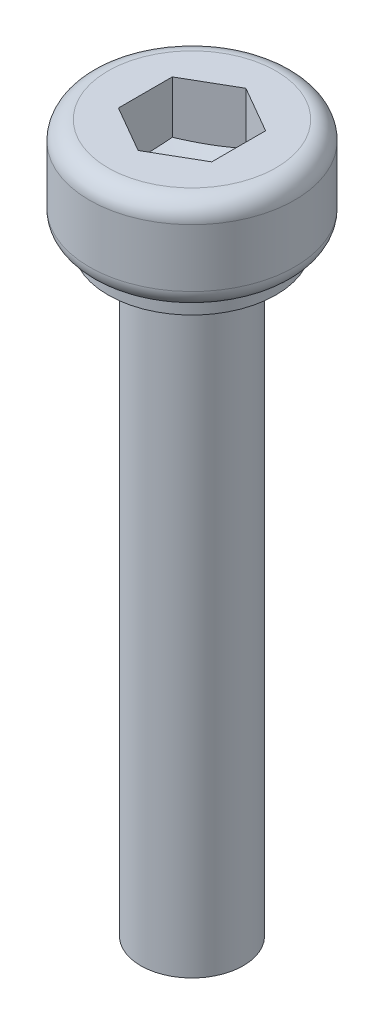
SolidWorks part; units mm, degrees
ref_plane "Front Plane" through (0, 0, 0) normal (0, 0, 1) x (1, 0, 0)
ref_plane "Top Plane" through (0, 0, 0) normal (0, 1, 0) x (1, 0, 0)
ref_plane "Right Plane" through (0, 0, 0) normal (1, 0, 0) x (0, 0, -1)
sketch "Sketch1" plane through (0, 0, 0) normal (0, 0, 1) x (1, 0, 0)
  line L0 (0, 4.0942) -> (0, -5.2249) construction
  line L1 (0, 9.475) -> (2.25, 9.475)
  line L2 (2.75, 8.975) -> (2.75, 7.425)
  line L3 (2.25, 6.525) -> (1.375, 6.525)
  line L4 (1.375, 6.525) -> (1.375, -9.475)
  line L5 (1.375, -9.475) -> (0, -9.475)
  line L6 (0, -9.475) -> (0, 9.475)
  line L7 (2.25, 6.525) -> (2.25, 6.925)
  line L8 (2.75, 6.525) -> (2.25, 6.525) construction
  line L9 (2.75, 7.425) -> (2.75, 6.525) construction
  line L10 (2.75, 9.475) -> (2.75, 8.975) construction
  line L11 (2.25, 9.475) -> (2.75, 9.475) construction
  arc A0 (2.25, 6.925) -> (2.75, 7.425) centre (2.25, 7.425) ccw
  arc A1 (2.25, 9.475) -> (2.75, 8.975) centre (2.25, 8.975) cw
  point P5 (0, 0)
  point P17 (0, 0)
  point P18 (0, 0)
  point P19 (2.25, 2.4541)
  dimension "D5" = 0.5
  dimension "D1" = 16
  dimension "D2" = 1.375
  dimension "D3" = 2.95
  dimension "D4" = 2.75
  dimension "D6" = 0.4
revolve "Revolve1" add sketch "Sketch1" angle 360 about L0
sketch "Sketch2" plane through (0, 9.475, 0) normal (0, 1, 0) x (1, 0, 0)
  line L1 (0, 1.4434) -> (-1.25, 0.7217)
  line L2 (-1.25, 0.7217) -> (-1.25, -0.7217)
  line L3 (-1.25, -0.7217) -> (0, -1.4434)
  line L4 (0, -1.4434) -> (1.25, -0.7217)
  line L5 (1.25, -0.7217) -> (1.25, 0.7217)
  line L6 (1.25, 0.7217) -> (0, 1.4434)
  circle A0 centre (0, 0) radius 1.25 construction
  dimension "D1" = 2.5
extrude "Boss-Extrude1" add sketch "Sketch2" against normal blind 2 separate body
sketch "Sketch3" plane through (0, 0, 0) normal (1, 0, 0) x (0, 0, -1)
  line L0 (0, 7.875) -> (0.4, 7.875)
  line L1 (0.4, 7.875) -> (1.4434, 8.075)
  line L2 (1.4434, 7.475) -> (1.4434, 9.475) construction
  line L3 (1.4434, 8.075) -> (1.4434, 7.475)
  line L4 (1.4434, 7.475) -> (0, 7.475)
  line L5 (-0.7217, 7.475) -> (0.7217, 7.475) construction
  line L6 (0, 7.475) -> (0, 7.875)
  line L7 (-0.7217, 9.475) -> (0.7217, 9.475) construction
  dimension "D1" = 1.6
  dimension "D2" = 1.4
  dimension "D3" = 0.4
revolve "Cut-Revolve1" cut sketch "Sketch3" angle 360 about L6
combine bodies "Combine1" operation type subtract main body 101 bodies to subtract 104
equation "\"Length\"= 16mm"
equation "\"D1@Sketch1\"=\"Length\""
equation "\"ThreadDiam\"= 2.75"
equation "\"D2@Sketch1\"=\"ThreadDiam\"/2"
equation "\"HeadHeight\"=2.95"
equation "\"D3@Sketch1\"=\"HeadHeight\""
equation "\"HeadDiam\"= 5.5"
equation "\"D4@Sketch1\"=\"HeadDiam\"/2"
equation "\"HexSize\"=2.5"
equation "\"D1@Sketch2\"=\"HexSize\""
